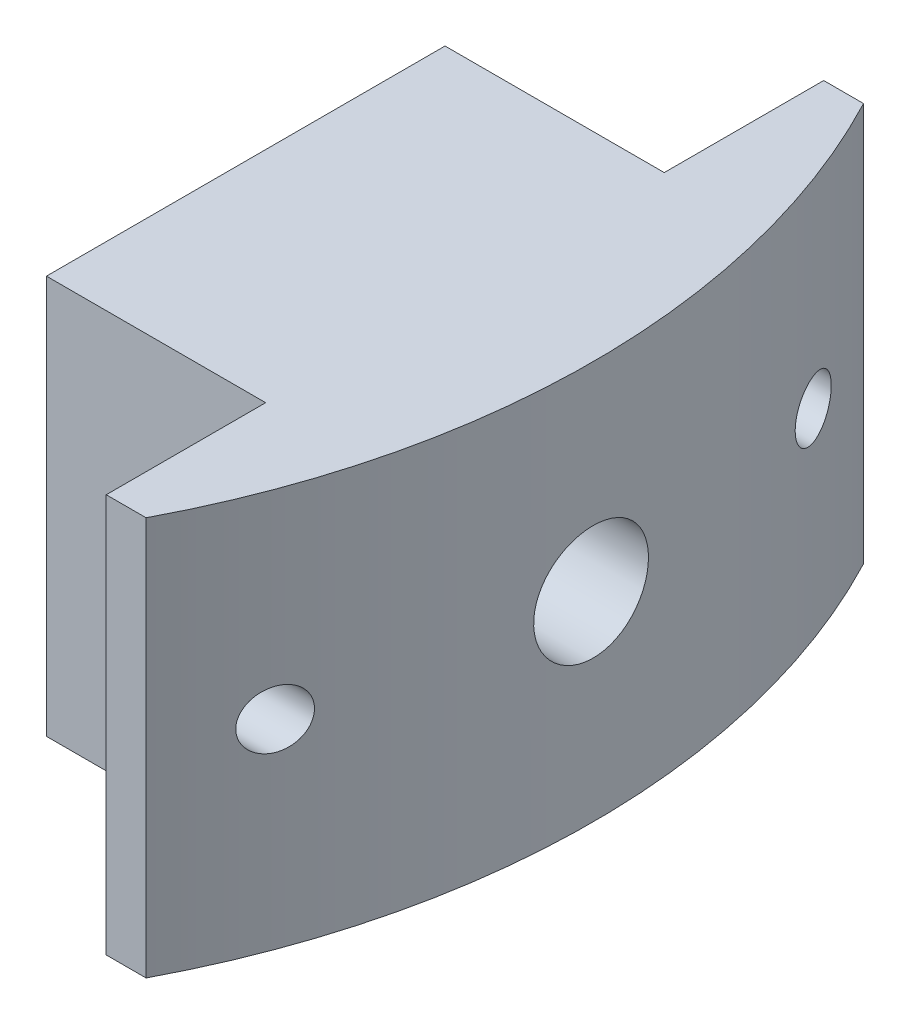
SolidWorks part; units mm, degrees
material "Plain Carbon Steel"
ref_plane "Front Plane" through (0, 0, 0) normal (0, 0, 1) x (1, 0, 0)
ref_plane "Top Plane" through (0, 0, 0) normal (0, 1, 0) x (1, 0, 0)
ref_plane "Right Plane" through (0, 0, 0) normal (1, 0, 0) x (0, 0, -1)
sketch "Sketch2" plane through (0, 0, 0) normal (0, 1, 0) x (1, 0, 0)
  line L0 (43.5809, 22.86) -> (43.5809, -22.86)
  line L1 (41.0409, 12.7) -> (41.0409, -12.7)
  line L2 (43.5809, 22.86) -> (41.0409, 22.86)
  line L3 (43.5809, 22.86) -> (43.5809, -22.86)
  line L4 (43.5809, -22.86) -> (41.0409, -22.86)
  line L5 (41.0409, 22.86) -> (41.0409, -22.86)
  line L6 (41.0409, 12.7) -> (27.0709, 12.7)
  line L11 (27.0709, 12.7) -> (27.0709, -12.7)
  line L12 (27.0709, -12.7) -> (41.0409, -12.7)
  line L13 (0, 0) -> (29.3279, 0) construction
  line L14 (0, 0) -> (47.5356, -12.7371) construction
  arc A0 (43.5809, -22.86) -> (43.5809, 22.86) centre (0, 0) ccw
  point P9 (41.0409, 0)
  dimension "D1" = 49.2125
  dimension "D2" = 45.72
  dimension "D3" = 2.54
  dimension "D4" = 25.4
  dimension "D5" = 13.97
  dimension "D6" = 15
extrude "Boss-Extrude1" add sketch "Sketch2" along normal blind 25.4 contours L11 L12 L1 L6 | L2 L5 L1 L4 L0 | L0 A0 | L0 A0 region at (45.8449, 0, 0) region at (42.3109, 0, 0) region at (34.0559, 0, 0)
ref_plane "Plane1" through (49.2125, 0, 0) normal (1, 0, 0) x (0, 0, -1)
sketch "Sketch4" plane through (27.0709, 0, 0) normal (-1, 0, 0) x (0, 0, 1)
  line L4 (-12.7, 0) -> (12.7, 25.4) construction
  line L5 (-12.7, 0) -> (12.7, 0) construction
  line L6 (-12.7, 25.4) -> (-12.7, 0) construction
  line L7 (-12.7, 25.4) -> (12.7, 0) construction
  line L8 (12.7, 25.4) -> (12.7, 0) construction
  line L9 (12.7, 25.4) -> (12.7, 0) construction
  circle A0 centre (0, 12.7) radius 3.81
  circle A1 centre (0, 12.7) radius 1.27
  point P15 (0, 12.7)
  dimension "D1" = 7.62
  dimension "D2" = 2.54
extrude "Cut-Extrude2" cut sketch "Sketch4" against normal up to next contours A1
sketch "Sketch11" plane through (41.0409, 0, 0) normal (-1, 0, 0) x (0, 0, 1)
  circle A2 centre (0, 12.7) radius 3.6576
  dimension "D3" = 7.3152
extrude "Cut-Extrude4" cut sketch "Sketch11" along normal blind 12.7 from surface contours A2 starting at plane "Plane1"
sketch "Sketch13" plane through (49.2125, 0, 0) normal (1, 0, 0) x (0, 0, -1)
  line L1 (-6.2992, 12.7) -> (-7.6327, 12.7) construction
  line L2 (-6.2992, 12.7) -> (-4.9657, 12.7) construction
  line L4 (0, 12.7) -> (-22.86, 12.7) construction
  line L5 (-22.86, 25.4) -> (-22.86, 0) construction
  circle A0 centre (0, 12.7) radius 4.9657
  circle A1 centre (0, 12.7) radius 7.6327
  circle A2 centre (0, 12.7) radius 6.2992 construction
  dimension "D1" = 12.5984
  dimension "D2" = 2.667
wrap "Wrap3" [suppressed] sketch "Sketch13" source sketch "Sketch13" thickness 1.3208 parameters "D1"=1.3208
sketch "Sketch15" plane through (0, 0, 0) normal (1, 0, 0) x (0, 0, -1)
  line L0 (-22.86, 12.7) -> (22.86, 12.7) construction
  line L1 (0, 0) -> (0, 25.4) construction
  line L4 (-22.86, 0) -> (22.86, 0)
  line L5 (22.86, 0) -> (22.86, 25.4)
  line L6 (22.86, 25.4) -> (-22.86, 25.4)
  line L7 (-22.86, 25.4) -> (-22.86, 0)
  line L8 (-22.86, 0) -> (22.86, 0)
  line L9 (22.86, 0) -> (22.86, 25.4)
  line L10 (22.86, 25.4) -> (-22.86, 25.4)
  line L11 (-22.86, 25.4) -> (-22.86, 0)
  circle A0 centre (-17.145, 12.7) radius 1.8288
  circle A1 centre (17.145, 12.7) radius 1.8288
  dimension "D2" = 3.6576
  dimension "D3" = 5.715
extrude "Cut-Extrude5" cut sketch "Sketch15" along normal up to surface (46.7684 mm away) contours L0 A0 | A1 region at (0, 12.7, 17.145) region at (0, 12.7, -17.145) up to face at (49.0834, 13.5299, 3.5622)
equation "\"Middle Coupler Inner Daimeter\"= 3.875in"
equation "\"Middle Coupler  Wall Thickness\"= 0.25in"
equation "\"Middle Coupler Bottom Thickness\"= 0.2in"
equation "\"Bearing Rail Offset\"= 0.45in"
equation "\"3-56 UNF Tap\"= 0.089in"
equation "\"3-48 Tap\"= 0.079in"
equation "\"3-56 UNF Clearance\"= 0.104in"
equation "\"3-48 Clearance\"= 0.104in"
equation "\"Ball Bearing Distance\"= 0.03in"
equation "\"TCA Outer Diameter\"= 6in"
equation "\"Interstage Aeroframe Wall Thickness\"= 0.072in"
equation "\"Compression Spring OD\"= 0.42in"
equation "\"10-24 Tap\"= 0.157in"
equation "\"10-24 Clearance\"= 0.196in"
equation "\"Lower Stage Fuselage Wall Thickness\"= 0.25in"
equation "\"6-32 Tap\"= 0.107in"
equation "\"6-32 Clearance\"= 0.144"
equation "\"1/4-20 Tap\"= 0.201in"
equation "\"12-24 Tap\"= 0.177in"
equation "\"D1@Sketch2\"=\"Middle Coupler Inner Daimeter\"/2"
equation "\"D2@Sketch15\"=\"6-32 Clearance\""
